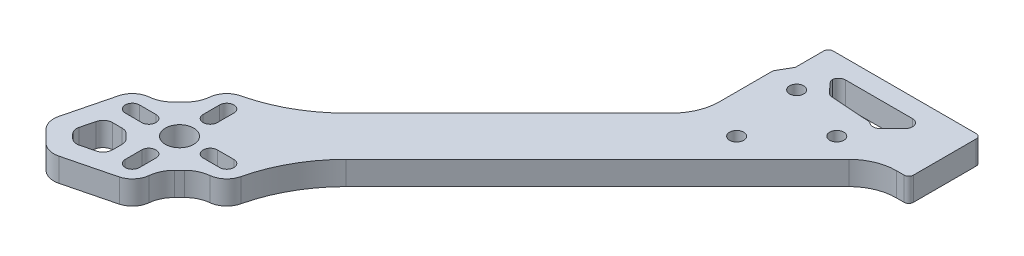
SolidWorks part; units mm, degrees
ref_plane "Front Plane" through (0, 0, 0) normal (0, 0, 1) x (1, 0, 0)
ref_plane "Top Plane" through (0, 0, 0) normal (0, 1, 0) x (1, 0, 0)
ref_plane "Right Plane" through (0, 0, 0) normal (1, 0, 0) x (0, 0, -1)
sketch "Sketch2" plane through (0, 0, 0) normal (0, 1, 0) x (1, 0, 0)
  line L0 (-39.4969, -89.7278) -> (17.9135, -32.3174)
  line L1 (9.4282, -17.0674) -> (9.4282, -32.3174) construction
  line L2 (9.4282, -32.3174) -> (24.6782, -32.3174) construction
  line L3 (-54.6599, -87.9202) -> (-9.3218, -42.5821)
  line L4 (-9.3218, -37.0674) -> (-9.3218, -42.5821)
  line L5 (9.4282, -32.3174) -> (24.6782, -17.0674) construction
  line L6 (-7.596, -17.0674) -> (24.6782, -17.0674)
  line L7 (-9.3218, -37.0674) -> (-9.3218, -17.0674)
  line L8 (24.6782, -17.0674) -> (24.6782, -32.3174)
  line L9 (9.4282, -17.0674) -> (-9.3218, -17.0674) construction
  line L10 (24.6782, -32.3174) -> (17.9135, -32.3174)
  line L13 (9.4282, -32.3174) -> (-14.0521, -55.7977) construction
  line L15 (-1.4599, -22.796) -> (1.0821, -25.5753)
  line L16 (1.0821, -25.5753) -> (10.2725, -26.2276)
  line L17 (10.2725, -26.2276) -> (11.7409, -27.1763)
  line L18 (9.4282, -17.0674) -> (24.6782, -17.0674) construction
  line L19 (24.6782, -32.3174) -> (24.6782, -17.0674) construction
  line L20 (13.4592, -28.2864) -> (13.2093, -28.125)
  line L21 (-60.1746, -101.9202) -> (-43.2974, -101.9202) construction
  line L22 (17.8498, -21.0674) -> (-1.4599, -21.0674)
  line L23 (-1.4599, -21.0674) -> (-1.4599, -22.796)
  line L24 (-14.0521, -55.7977) -> (-60.1746, -101.9202) construction
  line L25 (-60.1746, -101.9202) -> (-60.1746, -85.2433) construction
  line L26 (11.7409, -27.1763) -> (17.8498, -21.0674)
  line L27 (-60.1746, -101.9202) -> (-75.0152, -101.9202) construction
  line L28 (-60.1746, -101.9202) -> (-60.1746, -117.9623) construction
  line L29 (-7.596, -24.0674) -> (-9.326, -27.0674)
  line L30 (-53.6746, -101.9202) -> (-50.1746, -101.9202) construction
  line L31 (-7.596, -24.0674) -> (-7.596, -17.0674)
  line L32 (-53.6746, -100.4202) -> (-50.1746, -100.4202)
  line L33 (-53.6746, -103.4202) -> (-50.1746, -103.4202)
  line L34 (-60.1746, -108.4202) -> (-60.1746, -111.9202) construction
  line L35 (-58.6746, -108.4202) -> (-58.6746, -111.9202)
  line L36 (-61.6746, -108.4202) -> (-61.6746, -111.9202)
  line L37 (-66.6746, -101.9202) -> (-70.1746, -101.9202) construction
  line L38 (-66.6746, -103.4202) -> (-70.1746, -103.4202)
  line L39 (-66.6746, -100.4202) -> (-70.1746, -100.4202)
  line L40 (-60.1746, -95.4202) -> (-60.1746, -91.9202) construction
  line L41 (-61.6746, -95.4202) -> (-61.6746, -91.9202)
  line L42 (-58.6746, -95.4202) -> (-58.6746, -91.9202)
  line L43 (-70.1746, -97.9202) -> (-64.1746, -97.9202)
  line L44 (-64.1746, -91.9202) -> (-64.1746, -97.9202)
  line L45 (-56.1746, -111.9202) -> (-56.1746, -105.9202)
  line L46 (-50.1746, -105.9202) -> (-56.1746, -105.9202)
  line L47 (-77.1452, -113.2339) -> (-71.4883, -118.8908)
  line L48 (-39.4969, -89.7278) -> (-46.1894, -96.4203)
  line L49 (-60.1746, -87.9202) -> (-54.6599, -87.9202)
  line L50 (-46.1746, -101.9202) -> (-46.1894, -96.4203)
  line L51 (-71.4883, -118.8908) -> (-59.0474, -115.7581)
  line L52 (-77.1452, -113.2339) -> (-74.0537, -100.9444)
  line L53 (-72.7126, -112.0096) -> (-70.2645, -114.4577)
  line L54 (-70.2645, -114.4577) -> (-64.7708, -113.0744)
  line L55 (-64.7708, -113.0744) -> (-64.7708, -108.6377)
  line L56 (-64.7708, -108.6377) -> (-66.8921, -106.5164)
  line L57 (-66.8921, -106.5164) -> (-71.3308, -106.5164)
  line L58 (-71.3308, -106.5164) -> (-72.7126, -112.0096)
  line L59 (-72.7126, -112.0096) -> (-72.6759, -112.0237)
  circle A0 centre (-60.1746, -101.9202) radius 3
  circle A1 centre (-60.1746, -101.9202) radius 5 construction
  circle A2 centre (9.4282, -32.3174) radius 1.5
  arc A3 (-53.6746, -100.4202) -> (-53.6746, -103.4202) centre (-53.6746, -101.9202) ccw
  circle A4 centre (-60.1746, -101.9202) radius 12 construction
  arc A5 (-50.1746, -103.4202) -> (-50.1746, -100.4202) centre (-50.1746, -101.9202) ccw
  circle A6 centre (-1.1784, -42.924) radius 1.5
  arc A7 (-58.6746, -108.4202) -> (-61.6746, -108.4202) centre (-60.1746, -108.4202) ccw
  arc A8 (-61.6746, -111.9202) -> (-58.6746, -111.9202) centre (-60.1746, -111.9202) ccw
  arc A9 (-66.6746, -103.4202) -> (-66.6746, -100.4202) centre (-66.6746, -101.9202) ccw
  arc A10 (-70.1746, -100.4202) -> (-70.1746, -103.4202) centre (-70.1746, -101.9202) ccw
  arc A11 (-61.6746, -95.4202) -> (-58.6746, -95.4202) centre (-60.1746, -95.4202) ccw
  arc A12 (-58.6746, -91.9202) -> (-61.6746, -91.9202) centre (-60.1746, -91.9202) ccw
  arc A13 (-60.1746, -87.9202) -> (-64.1746, -91.9202) centre (-60.1746, -91.9202) ccw
  arc A14 (-50.1746, -105.9202) -> (-46.1746, -101.8987) centre (-50.1746, -101.9202) ccw
  circle A16 centre (-3.3218, -28.0674) radius 1.5
  arc A17 (-70.1746, -97.9202) -> (-74.0537, -100.9444) centre (-70.1746, -101.9202) ccw
  arc A18 (-59.0474, -115.7581) -> (-56.1746, -111.9202) centre (-60.1746, -111.9202) ccw
  point P36 (-51.9246, -101.9202)
  point P41 (-51.9246, -103.4202)
  point P47 (-60.1746, -110.1702)
  point P54 (-68.4246, -101.9202)
  point P63 (-60.1746, -93.6702)
  point P70 (-60.1746, -101.9202)
  dimension "D4" = 3
  dimension "D5" = 15.0104
  dimension "D9" = 3
  dimension "D24" = 8
  dimension "D25" = 8
  dimension "D2" = 3
  dimension "D15" = 6
  dimension "D16" = 10
  dimension "D17" = 24
  dimension "D18" = 3
  dimension "D21" = 4
  dimension "D22" = 8
  dimension "D23" = 4
  dimension "D35" = 4
  dimension "D6" = 45
  dimension "D7" = 13.4397
  dimension "D8" = 12
  dimension "D10" = 15
  dimension "D11" = 6
  dimension "D12" = 4
  dimension "D13" = 4
  dimension "D14" = 120
  dimension "D19" = 6.5
  dimension "D20" = 3.5
  dimension "D26" = 8
  dimension "D27" = 4
  dimension "D28" = 20
  dimension "D29" = 8
  dimension "D30" = 1.5
  dimension "D31" = 3
  dimension "D32" = 3
  dimension "D33" = 4
  dimension "D34" = 4
extrude "Boss-Extrude1" add sketch "Sketch2" along normal blind 5 contours L31 L29 L7 L4 L3 L0 L10 L8 L6 A16 A6 A2 L23 L22 L17 L16 L15 region at (-23.0581, 0, 62.7579)
fillet "Fillet1" radius 1.5 6 edges at (10.2725, 2.5, 26.2276) (1.0821, 2.5, 25.5753) (-1.4599, 2.5, 22.796) (-1.4599, 2.5, 21.0674) (11.7409, 2.5, 27.1763) (17.8498, 2.5, 21.0674)
fillet "Fillet3" radius 10 1 edges at (17.9135, 2.5, 32.3174)
fillet "Fillet5" radius 10 1 edges at (-9.3218, 2.5, 42.5821)
chamfer "Chamfer1" distance 4.5 angle 45 2 edges at (-64.1746, 2.5, 97.9202) (-56.1746, 2.5, 105.9202)
fillet "Fillet6" radius 6 4 edges at (-64.1746, 2.5, 93.4202) (-68.6746, 2.5, 97.9202) (-56.1746, 2.5, 110.4202) (-51.6746, 2.5, 105.9202)
fillet "Fillet7" radius 4 2 edges at (-71.4883, 2.5, 118.8908) (-77.1452, 2.5, 113.2339)
fillet "Fillet8" radius 2 6 edges at (-71.3308, 2.5, 106.5164) (-66.8921, 2.5, 106.5164) (-64.7708, 2.5, 108.6377) (-64.7708, 2.5, 113.0744) (-70.2645, 2.5, 114.4577) (-72.7126, 2.5, 112.0096)
fillet "Fillet9" radius 30 2 edges at (-54.6599, 2.5, 87.9202) (-46.1894, 2.5, 96.4203)
sketch "Sketch3" plane through (0, 5, 0) normal (0, 1, 0) x (1, 0, 0)
  circle A0 centre (-60.1746, -101.9202) radius 62.5
  dimension "D1" = 125
fillet "Fillet10" radius 1 3 edges at (24.6782, 2.5, 32.3174) (-7.596, 2.5, 17.0674) (24.6782, 2.5, 17.0674)
